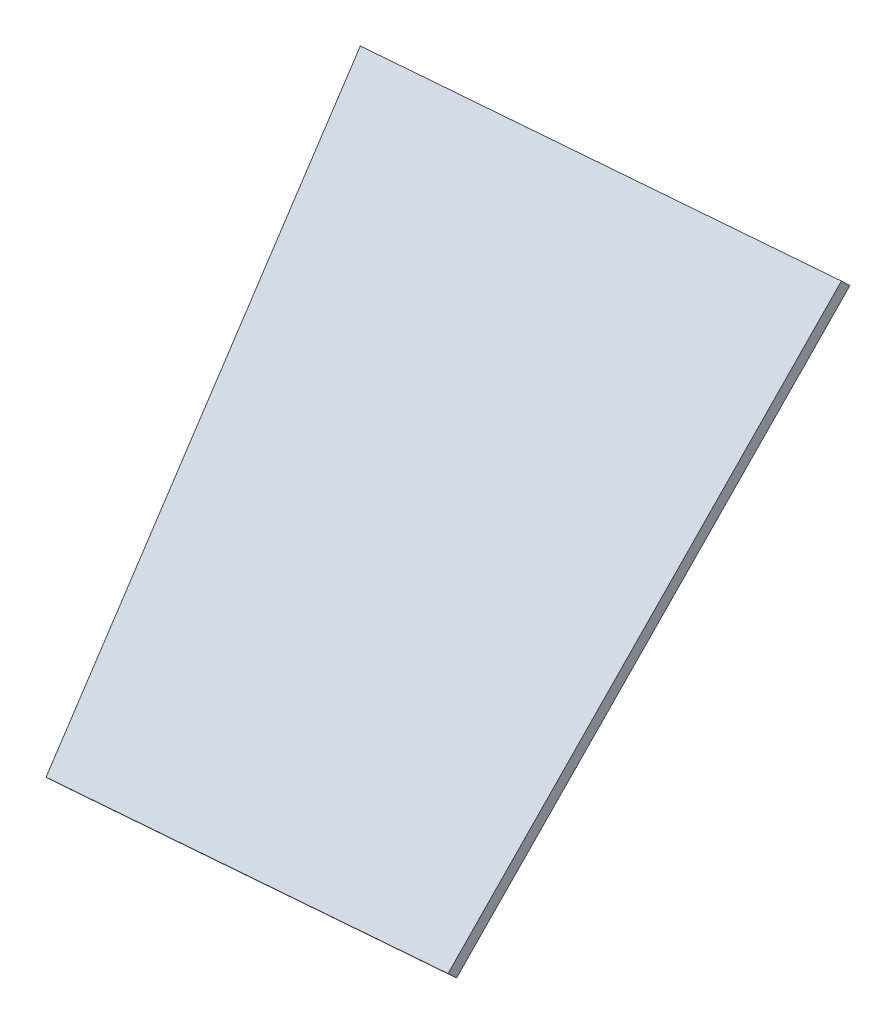
SolidWorks part; units mm, degrees
ref_plane "Front Plane" through (0, 0, 0) normal (0, 0, 1) x (1, 0, 0)
ref_plane "Top Plane" through (0, 0, 0) normal (0, 1, 0) x (1, 0, 0)
ref_plane "Right Plane" through (0, 0, 0) normal (1, 0, 0) x (0, 0, -1)
ref_plane "Pedlabox Floor Plane" through (100.3397, 1050.3908, 1100.2693) normal (-0.0658, -0.689, -0.7217) x (-0.9974, 0.0671, 0.0269)
sketch "PedalBox Floor" plane through (100.3397, 1050.3908, 1100.2693) normal (-0.0658, -0.689, -0.7217) x (-0.9974, 0.0671, 0.0269)
  line L0 (881.7376, -446.5868) -> (869.3494, -997.4757)
  line L1 (869.3494, -997.4757) -> (1230.9022, -1029.1413)
  line L2 (1230.9022, -1029.1413) -> (1314.4643, -484.486)
  line L3 (1314.4643, -484.486) -> (881.7376, -446.5868)
  line L4 (1285.0565, -481.9104) -> (911.1454, -449.1624) construction
  line L9 (1231.7093, -1023.8807) -> (1344.2606, -290.2747) construction
  line L10 (886.155, -250.1528) -> (869.4691, -992.1549) construction
  line L11 (1231.0433, -1029.1536) -> (869.2084, -997.4633) construction
extrude "Boss-Extrude1" add sketch "PedalBox Floor" along normal blind 12.7 contours L3 L0 L1 L2
